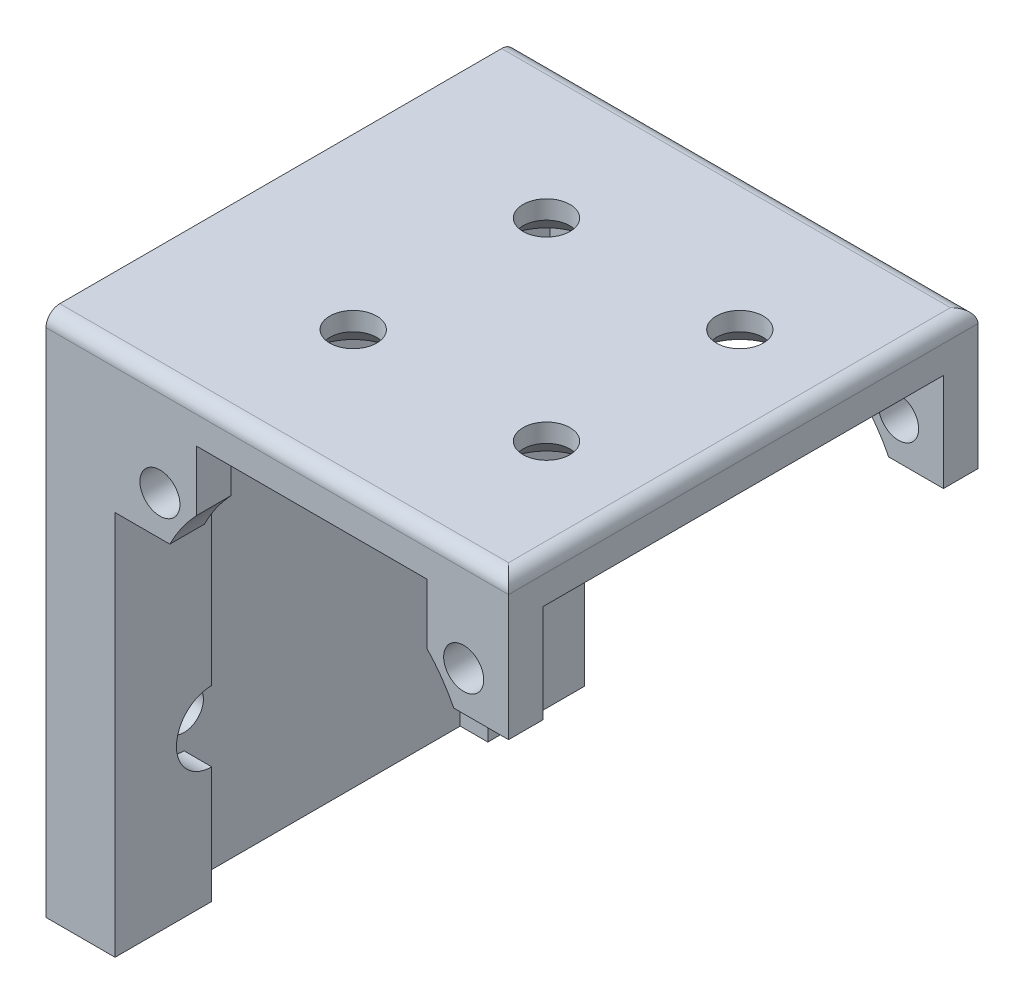
SolidWorks part; units mm, degrees
other "Markup1"
sketch "Sketch50" plane through (14.25, 15.25, -17) normal (0.1119, 0.5399, -0.8342) x (-0.9073, -0.2868, -0.3074)
ref_plane "Front Plane" through (0, 0, 0) normal (0, 0, 1) x (1, 0, 0)
ref_plane "Top Plane" through (0, 0, 0) normal (0, 1, 0) x (1, 0, 0)
ref_plane "Right Plane" through (0, 0, 0) normal (1, 0, 0) x (0, 0, -1)
sketch "Sketch1" plane through (0, 0, 0) normal (0, 0, 1) x (1, 0, 0)
  line L0 (0, 0) -> (0, 5.0753) construction
  line L1 (-14.25, 11.25) -> (14.25, 11.25)
  line L2 (-14.25, 11.25) -> (-14.25, -35.25)
  line L3 (-14.25, -35.25) -> (14.25, -35.25)
  line L4 (14.25, 11.25) -> (14.25, -35.25)
  line L5 (-14.25, 11.25) -> (-7.75, 11.25)
  line L6 (-14.25, 11.25) -> (-14.25, 4.75)
  line L7 (-14.25, 4.75) -> (-7.75, 4.75)
  line L8 (-7.75, 11.25) -> (-7.75, 4.75)
  line L9 (0, 0) -> (3.7441, 0) construction
  line L10 (14.25, 4.75) -> (7.75, 4.75)
  line L11 (7.75, 11.25) -> (7.75, 4.75)
  line L12 (-14.25, -12) -> (23.601, -12) construction
  line L13 (7.75, -35.25) -> (7.75, -29.75)
  line L14 (14.25, -28.75) -> (8.75, -28.75)
  line L15 (-7.75, -35.25) -> (-7.75, -29.75)
  line L16 (-14.25, -28.75) -> (-8.75, -28.75)
  line L18 (14.25, 11.25) -> (-14.25, 11.25)
  line L19 (14.25, 11.25) -> (14.25, 15.25)
  line L20 (14.25, 15.25) -> (-14.25, 15.25)
  line L21 (-14.25, 11.25) -> (-14.25, 15.25)
  line L22 (-14.25, 4.75) -> (-16.25, 4.75)
  line L23 (-14.25, 4.75) -> (-14.25, 15.25)
  line L24 (-14.25, 15.25) -> (-16.25, 15.25)
  line L25 (-16.25, 4.75) -> (-16.25, 15.25)
  line L26 (14.25, 15.25) -> (16.25, 15.25)
  line L27 (14.25, 15.25) -> (14.25, 4.75)
  line L28 (14.25, 4.75) -> (16.25, 4.75)
  line L29 (16.25, 15.25) -> (16.25, 4.75)
  line L30 (-8.25, 11.25) -> (8.25, 11.25)
  line L31 (-8.25, 11.25) -> (-8.25, 4.75)
  line L32 (-8.25, 4.75) -> (8.25, 4.75)
  line L33 (8.25, 11.25) -> (8.25, 4.75)
  line L34 (-8.25, 11.25) -> (8.25, 11.25)
  line L35 (-8.25, 11.25) -> (-8.25, 12.25)
  line L36 (-8.25, 12.25) -> (8.25, 12.25)
  line L37 (8.25, 11.25) -> (8.25, 12.25)
  circle A1 centre (0, 0) radius 10.45
  circle A2 centre (-11, 8) radius 1.45
  circle A3 centre (11, 8) radius 1.45
  circle A4 centre (11, -32) radius 1.45
  circle A5 centre (-11, -32) radius 1.45
  arc A7 (-7.75, -29.75) -> (-8.75, -28.75) centre (-8.75, -29.75) ccw
  arc A8 (8.75, -28.75) -> (7.75, -29.75) centre (8.75, -29.75) ccw
  circle A9 centre (0, 0) radius 11.5
  point P0 (0, 0)
  point P35 (-7.75, -28.75)
  point P38 (7.75, -28.75)
  dimension "D1" = 28.5
  dimension "D2" = 46.5
  dimension "D3" = 23
  dimension "D4" = 11.25
  dimension "D5" = 2.9
  dimension "D6" = 3.25
  dimension "D7" = 3.25
  dimension "D10" = 3.25
  dimension "D12" = 1
  dimension "D16" = 20.9
  dimension "D17" = 0.5
  dimension "D11" = 3.25
  dimension "D13" = 4
  dimension "D14" = 2
  dimension "D15" = 2
  dimension "D18" = 0.5
  dimension "D19" = 1
  dimension "D8" = 2
  dimension "D9" = 2
extrude "Boss-Extrude7" add sketch "Sketch1" along normal blind 17 and the other way blind 17 contours L37 L18 L19 L20 L21 L1 L35 L36 | A9 L10 L4 L18 L33 A3 | A9 L31 L1 L2 L7 A2 region at (0, 13.5038, 0) region at (-11.25, 11.1615, 0) region at (14.1615, 8, 0)
sketch "Sketch34" plane through (-14.25, 0, 0) normal (-1, 0, 0) x (0, 0, 1)
  line L0 (-17, 4.75) -> (17, 4.75) construction
  line L1 (-14.2, 12.25) -> (14.2, 12.25)
  line L2 (-14.2, 12.25) -> (-14.2, 4.75)
  line L3 (-14.2, 4.75) -> (14.2, 4.75)
  line L4 (14.2, 12.25) -> (14.2, 4.75)
  line L5 (-17, 4.75) -> (-17, 15.25) construction
  line L6 (17, 4.75) -> (17, 15.25) construction
  line L7 (-17, 15.25) -> (17, 15.25) construction
  dimension "D1" = 2.8
  dimension "D2" = 2.8
  dimension "D3" = 3
extrude "Cut-Extrude11" cut sketch "Sketch34" against normal through all
sketch "Sketch35" plane through (0, 15.25, 0) normal (0, 1, 0) x (1, 0, 0)
  circle A0 centre (0, 0) radius 5
extrude "Cut-Extrude12" cut sketch "Sketch35" against normal through all
sketch "Sketch39" plane through (0, 12.25, 0) normal (0, -1, 0) x (1, 0, 0)
  line L0 (-14.25, 14.2) -> (-14.25, -14.2) construction
  line L1 (-8.25, 17) -> (8.25, 17) construction
  line L3 (0, 0) -> (0, 7.1623) construction
  line L4 (0, 0) -> (6.1391, 0) construction
  circle A0 centre (-8.25, 9) radius 1.5
  circle A1 centre (8.25, 9) radius 1.5
  circle A2 centre (-8.25, -9) radius 1.5
  circle A3 centre (8.25, -9) radius 1.5
  point P0 (-8.25, 9)
  point P9 (8.25, 9)
  point P12 (-8.25, -9)
  point P14 (8.25, -9)
  dimension "D1" = 6
  dimension "D2" = 8
hole_wizard "CSK for M3 Hex Socket Countersunk Cap Screw3" positions "Sketch39" profile "Sketch40" countersink size "M3" standard "ISO" end condition through all
sketch "Sketch40" plane through (-8.25, 12.25, 9) normal (1, 0, 0) x (0, 0, -1)
  line L0 (0, 0) -> (0, 3)
  line L1 (0, 3) -> (1.7, 3)
  line L2 (1.7, 3) -> (1.7, 1.66)
  line L3 (1.7, 1.66) -> (3.36, 0)
  line L5 (3.36, 0) -> (0, 0)
  line L6 (-1.7, 1.66) -> (-3.36, 0) construction
  line L11 (0, -6.35) -> (0, 107.95) construction
  dimension "Thru Hole Dia." = 3.4
  dimension "Thru Hole Depth" = 3
  dimension "Near C'Sink Dia." = 6.72
  dimension "Near C'Sink Angle" = 90
fillet "Fillet5" radius 1 3 edges at (14.25, 15.25, 0) (0, 15.25, -17) (0, 15.25, 17)
sketch "Sketch41" plane through (0, 0, 17) normal (0, 0, 1) x (1, 0, 0)
  line L0 (14.25, 4.75) -> (14.25, 14.25) construction
  line L1 (-14.25, 4.75) -> (14.25, 4.75)
  line L2 (-14.25, 4.75) -> (-14.25, 5.15)
  line L3 (-14.25, 5.15) -> (14.25, 5.15)
  line L4 (14.25, 4.75) -> (14.25, 5.15)
  dimension "D1" = 0.4
extrude "Cut-Extrude13" cut sketch "Sketch41" against normal through all
sketch "Sketch45" plane through (0, 0, 17) normal (0, 0, 1) x (1, 0, 0)
  circle A0 centre (11, 8) radius 1.45
  circle A1 centre (0, 0) radius 11.5
sketch "Sketch46" plane through (-14.25, 0, 0) normal (-1, 0, 0) x (0, 0, 1)
  line L1 (16, 15.25) -> (17, 15.25)
  line L4 (17, 15.25) -> (17, 14.25)
  line L5 (17, 15.25) -> (-17, 15.25)
  line L6 (17, 15.25) -> (17, -22.75)
  line L7 (17, -22.75) -> (-17, -22.75)
  line L8 (-17, 15.25) -> (-17, -22.75)
  line M3 (-17, 14.25) -> (-17, 5.15)
  line M4 (-17, 5.15) -> (-14.2, 5.15)
  line M5 (-14.2, 5.15) -> (-14.2, 12.25)
  line M6 (-14.2, 12.25) -> (14.2, 12.25)
  line M7 (14.2, 12.25) -> (14.2, 5.15)
  line M8 (14.2, 5.15) -> (17, 5.15)
  line M9 (17, 5.15) -> (17, 14.25)
  arc M10 (17, 14.25) -> (16, 15.25) centre (16, 14.25) ccw
  line M11 (16, 15.25) -> (-16, 15.25)
  arc M12 (-16, 15.25) -> (-17, 14.25) centre (-16, 14.25) ccw
  dimension "D1" = 34
  dimension "D2" = 38
extrude "Boss-Extrude8" add sketch "Sketch46" along normal blind 5 contours L8 L7 L6 M4 M8 M7 M6 M5 | M12 M3 M4 M5 M6 M7 M8 M9 M10 M11 region at (-14.25, 12.3254, 0) region at (-14.25, -5.7322, 0)
sketch "Sketch48" plane through (-19.25, 0, 0) normal (-1, 0, 0) x (0, 0, 1)
  line L0 (17, -22.75) -> (-17, -22.75) construction
  line L1 (-17, 14.25) -> (-17, -22.75) construction
  circle A0 centre (-10, -11.75) radius 1.4
  circle A1 centre (10, -11.75) radius 1.4
  circle A2 centre (10, 4.25) radius 1.4
  circle A3 centre (-10, 4.25) radius 1.4
  dimension "D1" = 11
  dimension "D2" = 7
  dimension "D5" = 27
  dimension "D6" = 20
  dimension "D7" = 16
  dimension "D3" = 2
  dimension "D4" = 2
extrude "Cut-Extrude14" cut sketch "Sketch48" against normal blind 5
sketch "Sketch49" plane through (-14.25, 0, 0) normal (1, 0, 0) x (0, 0, -1)
  line L0 (-17, -22.75) -> (17, -22.75) construction
  line L1 (-17, 5.15) -> (-17, -22.75) construction
  circle A1 centre (-10, -11.75) radius 2.55
  circle A2 centre (10, -11.75) radius 2.55
  circle A3 centre (10, 4.25) radius 2.55
  circle A4 centre (-10, 4.25) radius 2.55
  dimension "D1" = 5.1
  dimension "D2" = 11
  dimension "D3" = 7
  dimension "D4" = 2
  dimension "D5" = 2
extrude "Cut-Extrude15" cut sketch "Sketch49" against normal blind 2
sketch "Sketch51" plane through (0, 15.25, 0) normal (0, 1, 0) x (1, 0, 0)
  line L1 (-12.4259, 14.9747) -> (12.4259, 14.9747)
  line L2 (-12.4259, 14.9747) -> (-12.4259, -14.9747)
  line L3 (-12.4259, -14.9747) -> (12.4259, -14.9747)
  line L4 (12.4259, 14.9747) -> (12.4259, -14.9747)
  line L5 (-12.4259, 14.9747) -> (12.4259, -14.9747) construction
  line L6 (-12.4259, -14.9747) -> (12.4259, 14.9747) construction
  point P0 (0, 0)
extrude "Boss-Extrude9" add sketch "Sketch51" against normal blind 3
sketch "Sketch52" plane through (0, 12.25, 0) normal (0, -1, 0) x (1, 0, 0)
  line L5 (-8.25, 17) -> (8.25, 17) construction
  line L6 (-14.25, 14.2) -> (-14.25, -14.2) construction
  circle A1 centre (-7, 7) radius 1.5
  circle A2 centre (7, 7) radius 1.5
  circle A3 centre (7, -7) radius 1.5
  circle A4 centre (-7, -7) radius 1.5
  point P7 (-7, -7)
  point P8 (-7, 7)
  point P9 (7, -7)
  point P16 (7, 7)
  point P17 (-7, 7)
  dimension "D3" = 2
  dimension "D1" = 10
  dimension "D2" = 7.25
  dimension "D4" = 2
hole_wizard "CSK for M3 Hex Socket Countersunk Cap Screw4" positions "Sketch52" profile "Sketch53" countersink size "M3" standard "ISO" end condition through all
sketch "Sketch53" plane through (-7, 12.25, 7) normal (1, 0, 0) x (0, 0, -1)
  line L0 (0, 0) -> (0, 3)
  line L1 (0, 3) -> (1.7, 3)
  line L2 (1.7, 3) -> (1.7, 1.66)
  line L3 (1.7, 1.66) -> (3.36, 0)
  line L5 (3.36, 0) -> (0, 0)
  line L6 (-1.7, 1.66) -> (-3.36, 0) construction
  line L11 (0, -6.35) -> (0, 107.95) construction
  dimension "Thru Hole Dia." = 3.4
  dimension "Thru Hole Depth" = 3
  dimension "Near C'Sink Dia." = 6.72
  dimension "Near C'Sink Angle" = 90
sketch "Sketch54" plane through (-14.25, 0, 0) normal (1, 0, 0) x (0, 0, -1)
  line L0 (-17, -22.75) -> (17, -22.75) construction
  line L1 (-10, 4.25) -> (10, 4.25)
  line L2 (-10, 4.25) -> (-10, -11.75)
  line L3 (-10, -11.75) -> (10, -11.75)
  line L4 (10, 4.25) -> (10, -11.75)
  line L5 (-10, -11.75) -> (10, -11.75)
  line L6 (-10, -11.75) -> (-10, -22.75)
  line L7 (-10, -22.75) -> (10, -22.75)
  line L8 (10, -11.75) -> (10, -22.75)
  circle M1 centre (-10, 4.25) radius 2.55
  circle M2 centre (10, 4.25) radius 2.55
  circle M3 centre (10, -11.75) radius 2.55
  circle M4 centre (-10, -11.75) radius 2.55
  line M12 (-17, -22.75) -> (17, -22.75)
extrude "Cut-Extrude20" cut sketch "Sketch54" against normal blind 2 contours L4 L1 L2 L3 M2 M1 M4 M3 | L8 L3 L6 M3 M4 M12 | L1 L2 M1 | L4 L1 M2 | L8 L3 M3 | L4 L3 M3 | L3 L6 M4 | L2 L3 M4 region at (-14.25, 3.1677, 8.9177) region at (-14.25, -3.75, 0) region at (-14.25, 3.1677, -8.9177) region at (-14.25, -10.6677, 8.9177) region at (-14.25, -12.8323, 8.9177) region at (-14.25, -17.4651, 0) region at (-14.25, -10.6677, -8.9177) region at (-14.25, -12.8323, -8.9177)
sketch "Sketch55" plane through (14.25, 0, 0) normal (1, 0, 0) x (0, 0, -1)
  line L0 (-14.2, 5.15) -> (-17, 5.15) construction
  line L1 (-14.5, 5.15) -> (14.5, 5.15)
  line L2 (-14.5, 5.15) -> (-14.5, 12.25)
  line L3 (-14.5, 12.25) -> (14.5, 12.25)
  line L4 (14.5, 5.15) -> (14.5, 12.25)
  line L5 (-14.2, 5.15) -> (-14.2, 12.25) construction
  line L6 (14.2, 12.25) -> (14.2, 5.15) construction
  dimension "D1" = 0.3
  dimension "D2" = 0.3
extrude "Cut-Extrude21" cut sketch "Sketch55" against normal blind 28.5
sketch "Sketch56" plane through (0, 0, 17) normal (0, 0, 1) x (1, 0, 0)
  line L0 (-8.25, 8.0117) -> (-8.25, 12.25) construction
  line L1 (-8.35, 12.266) -> (8.35, 12.266)
  line L2 (-8.35, 12.266) -> (-8.35, 6.6589)
  line L3 (-8.35, 6.6589) -> (8.35, 6.6589)
  line L4 (8.35, 12.266) -> (8.35, 6.6589)
  line L5 (8.25, 8.0117) -> (8.25, 12.25) construction
  dimension "D1" = 0.1
  dimension "D2" = 0.1
extrude "Cut-Extrude22" cut sketch "Sketch56" against normal blind 34
